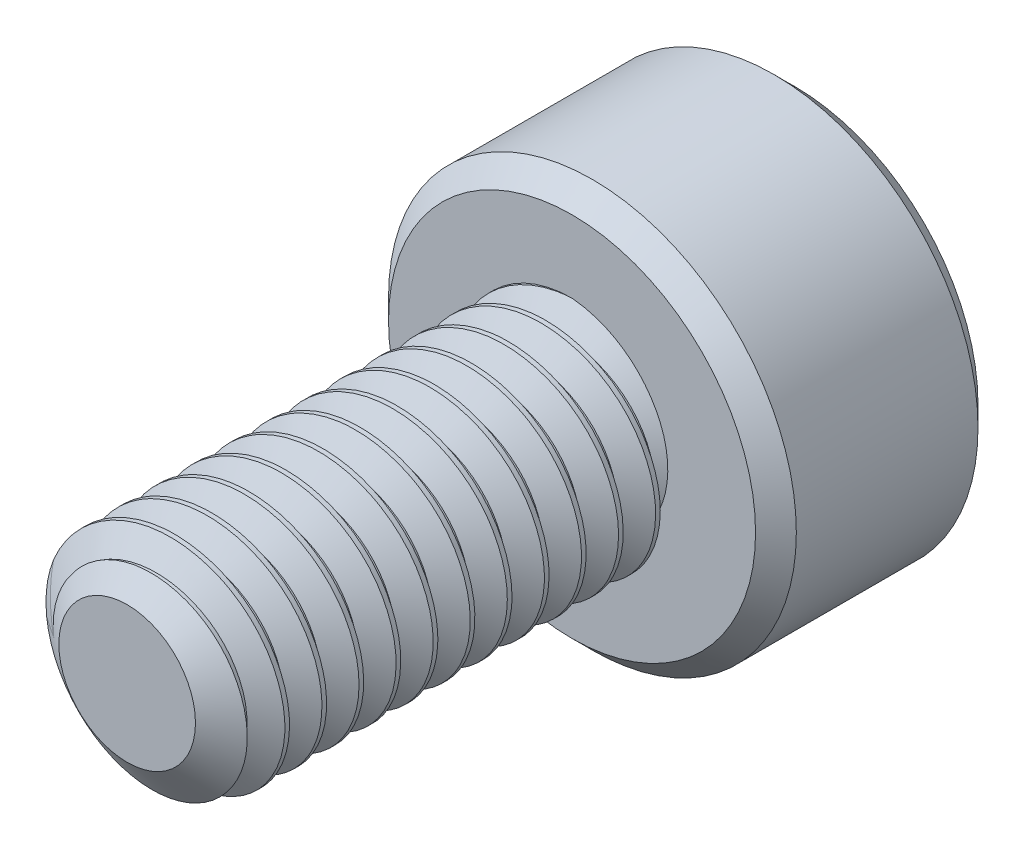
SolidWorks part; units mm, degrees
other "DetailItem1"
ref_plane "Front Plane" through (0, 0, 0) normal (0, 0, 1) x (1, 0, 0)
ref_plane "Top Plane" through (0, 0, 0) normal (0, 1, 0) x (1, 0, 0)
ref_plane "Right Plane" through (0, 0, 0) normal (1, 0, 0) x (0, 0, -1)
sketch "Sketch1" plane through (0, 0, 0) normal (0, 0, 1) x (1, 0, 0)
  circle A0 centre (0, 0) radius 1.5
  dimension "OD" = 3
extrude "Extrude1" add sketch "Sketch1" against normal blind 6
sketch "Sketch2" plane through (0, 0, 0) normal (0, 0, 1) x (1, 0, 0)
  circle A0 centre (0, 0) radius 1.5 construction
  circle A1 centre (0, 0) radius 1.5
curve "Helix/Spiral1" pitch 0.5 height 6.5 radius 1.5 centre (0, 0, 0) axis (0, 0, -1) start towards (0, 1, 0) parameters "pitch"=0.5
sketch "Sketch3" plane through (0, 0, 0) normal (1, 0, 0) x (0, 0, -1)
  line L0 (-0.4375, 1.5) -> (-0.25, 1.1752)
  line L1 (-0.25, 1.1752) -> (-0.1875, 1.1752)
  line L2 (-0.1875, 1.1752) -> (0, 1.5)
  line L3 (-0.4375, 1.5) -> (0, 1.5)
  line L4 (-0.2188, 1.5) -> (-0.2188, 1.1752) construction
  line L5 (-0.3438, 1.3376) -> (-0.0938, 1.3376) construction
  line L6 (0, 1.5) -> (0, -1.5) construction
  dimension "D2" = 0.25
  dimension "D3" = 60
sweep "Cut-Sweep1" cut profiles "Sketch3" path "Helix/Spiral1" align with end faces yes
sketch "Sketch4" plane through (0, 0, 0) normal (1, 0, 0) x (0, 0, -1)
  line L0 (0.4053, 1.5) -> (0, 0.9212)
  line L1 (0, 0.9212) -> (0, 1.5)
  line L2 (0.4053, 1.5) -> (0, 1.5)
  line L3 (-0.4375, 1.5) -> (0, 1.5) construction
  line L4 (0, 0) -> (7.0209, 0) construction
  dimension "D1" = 55
  dimension "D2" = 0.254
revolve "Cut-Revolve1" cut sketch "Sketch4" angle 360 about L4
sketch "Sketch6" plane through (0, 0, -6) normal (0, 0, -1) x (-1, 0, 0)
  circle A0 centre (0, 0) radius 2.75
  dimension "head dia" = 5.5
extrude "Extrude2" add sketch "Sketch6" along normal blind 3
sketch "Sketch7" plane through (0, 0, -9) normal (0, 0, -1) x (-1, 0, 0)
  line L1 (0, 1.4434) -> (-1.25, 0.7217)
  line L2 (-1.25, 0.7217) -> (-1.25, -0.7217)
  line L3 (-1.25, -0.7217) -> (0, -1.4434)
  line L4 (0, -1.4434) -> (1.25, -0.7217)
  line L5 (1.25, -0.7217) -> (1.25, 0.7217)
  line L6 (1.25, 0.7217) -> (0, 1.4434)
  circle A0 centre (0, 0) radius 1.25 construction
  dimension "hex dia" = 2.5
extrude "Cut-Extrude1" cut sketch "Sketch7" against normal blind 1.875
sketch "Sketch8" plane through (0, 0, -9) normal (0, 0, -1) x (-1, 0, 0)
  circle A0 centre (0, 0) radius 1.4434
extrude "Cut-Extrude2" cut sketch "Sketch8" against normal through all draft 45
chamfer "Chamfer1" distance 0.275 angle 45 2 edges at (-2.75, 0, -9) (-2.75, 0, -6)
sketch "Sketch10" plane through (0, 0, -6) normal (0, 0, 1) x (1, 0, 0)
  circle A1 centre (0, 0) radius 1.5
  circle A2 centre (0, 0) radius 1.5
  dimension "D1" = 0
ref_plane "Plane1" through (0, 0, -22) normal (0, 0, 1) x (1, 0, 0)
extrude "partial thread" [suppressed] add sketch "Sketch10" along normal up to surface (58 mm away) separate body up to plane "Plane1"
chamfer "Chamfer2" [suppressed] distance 0.06 angle 45
combine bodies "Combine1" [suppressed] operation type add bodies to combine 107 108
sketch "Sketch9" plane through (0, 0, 0) normal (1, 0, 0) x (0, 0, -1)
  line L0 (0, 1.5) -> (0, -1.5) construction
  line L1 (1.25, 1.5) -> (1.25, -1.5) construction
  dimension "D1" = 1.25
equation "\"D3@Helix/Spiral1\" = \"screw length@Extrude1\"+\"pitch@Helix/Spiral1\""
equation "\"D1@Sketch3\" = \"pitch@Helix/Spiral1\"*.125"
equation "\"D2@Sketch3\" = \"pitch@Helix/Spiral1\"*.5"
equation "\"D1@Cut-Extrude1\" = \"hex dia@Sketch7\"*.75"
equation "\"D1@Chamfer1\" = \"head dia@Sketch6\"*.05"
equation "\"D1@Sketch9\" = \"pitch@Helix/Spiral1\"*2.5"
equation "\"D1@Chamfer2\"=\"OD@Sketch1\"*.02"
